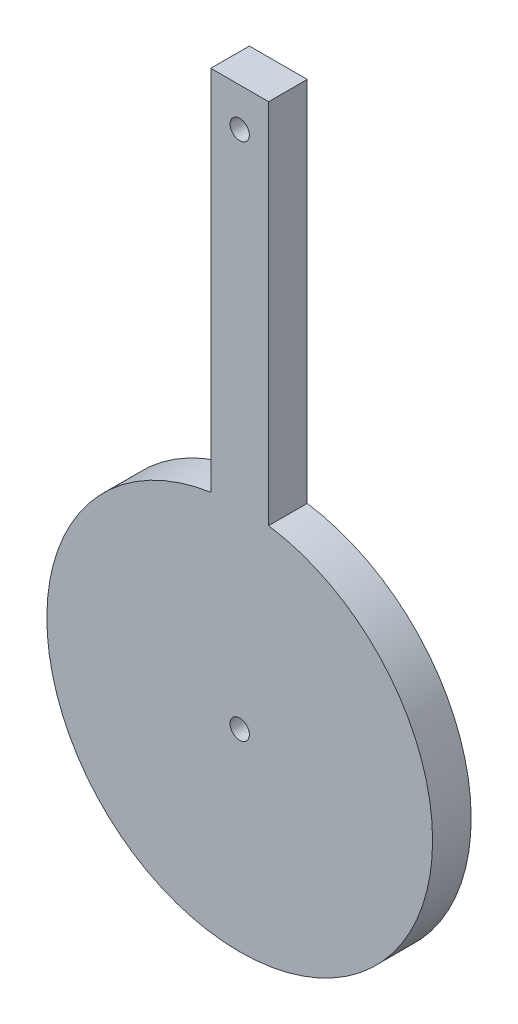
SolidWorks part; units mm, degrees
material "Custom Plastic"
ref_plane "Front Plane" through (0, 0, 0) normal (0, 0, 1) x (1, 0, 0)
ref_plane "Top Plane" through (0, 0, 0) normal (0, 1, 0) x (1, 0, 0)
ref_plane "Right Plane" through (0, 0, 0) normal (1, 0, 0) x (0, 0, -1)
sketch "Sketch2" plane through (0, 0, 0) normal (0, 0, 1) x (1, 0, 0)
  line L0 (7.5, 49.4343) -> (7.5, 144.62)
  line L1 (7.5, 144.62) -> (-7.5, 144.62)
  line L2 (-7.5, 144.62) -> (-7.5, 49.4343)
  line L3 (0, 0) -> (0, 144.62) construction
  arc A0 (-7.5, 49.4343) -> (7.5, 49.4343) centre (0, 0) ccw
  dimension "D1" = 50
  dimension "D2" = 15
  dimension "D3" = 15
  dimension "D4" = 144.62
base flange "Base-Flange1" sketch "Sketch2" thickness 10 reverse thickness direction no parameters "D1"=0.7366
sketch "Sketch7" plane through (0, 0, 0) normal (0, 0, 1) x (1, 0, 0)
  line L0 (7.5, 144.62) -> (-7.5, 144.62) construction
  line L1 (7.5, 49.4343) -> (7.5, 144.62) construction
  circle A0 centre (0, 134.62) radius 2.5
  circle A1 centre (0, 0) radius 2.5
  point P2 (0, 144.62)
  dimension "D1" = 5
  dimension "D2" = 10
  dimension "D3" = 7.5
extrude "Cut-Extrude1" cut sketch "Sketch7" against normal up to next normal cut yes
sketch "Bend-Lines1" [suppressed] plane through (0, 0, 0) normal (0, 1, 0) x (1, 0, 0)
sketch "Bounding-Box1" [suppressed] plane through (0, 0, 0) normal (0, 1, 0) x (1, 0, 0)
sheet metal parameters "Sheet-Metal1" thickness 10 parameters "D1"=0.7366
flat pattern "Flat-Pattern1" [suppressed]
sketch "Bend-Lines2" plane through (0, 0, 0) normal (0, 1, 0) x (1, 0, 0)
sketch "Bounding-Box2" [suppressed] plane through (0, 0, 0) normal (0, 1, 0) x (1, 0, 0)
sheet metal parameters "Sheet-Metal2" thickness 10 parameters "D1"=0.7366
flat pattern "Flat-Pattern1"
sketch "Bend-Lines2" plane through (0, 0, 0) normal (0, 1, 0) x (1, 0, 0)
sketch3d "Bounding-Box2" [suppressed]
  line L0 (35.6127, -61.0879, 0) -> (90.1741, 146.02, 0) construction
  line L1 (-61.0879, -35.6127, 0) -> (-6.5265, 171.4952, 0) construction
  line L2 (35.6127, -61.0879, 0) -> (-61.0879, -35.6127, 0) construction
  line L3 (90.1741, 146.02, 0) -> (-6.5265, 171.4952, 0) construction
